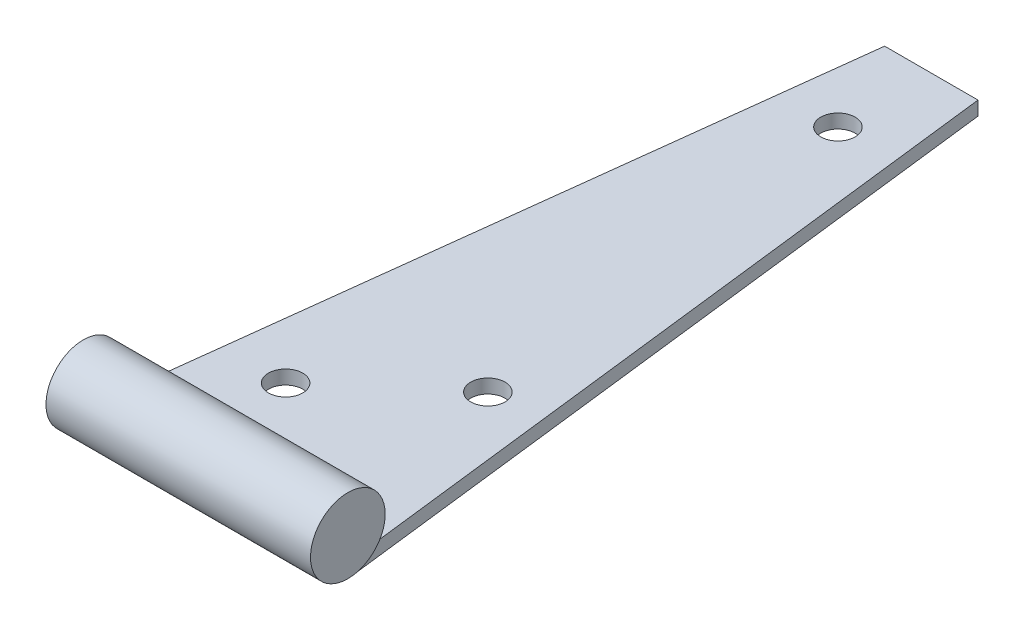
SolidWorks part; units mm, degrees
ref_plane "Front Plane" through (0, 0, 0) normal (0, 0, 1) x (1, 0, 0)
ref_plane "Top Plane" through (0, 0, 0) normal (0, 1, 0) x (1, 0, 0)
ref_plane "Right Plane" through (0, 0, 0) normal (1, 0, 0) x (0, 0, -1)
sketch "Sketch1" plane through (0, 0, 0) normal (0, 1, 0) x (1, 0, 0)
  line L0 (0, 0) -> (26.9875, 0)
  line L1 (13.4937, 0) -> (13.4937, 73.025) construction
  line L2 (18.2562, 73.025) -> (8.7312, 73.025)
  line L5 (0, 0) -> (8.7312, 73.025)
  line L6 (18.2562, 73.025) -> (26.9875, 0)
  point P8 (13.4937, 73.025)
extrude "Boss-Extrude1" add sketch "Sketch1" along normal blind 1.4224
sketch "Sketch2" plane through (0, 0, 0) normal (1, 0, 0) x (0, 0, -1)
  line L0 (0, 0) -> (0, 3.81) construction
  circle A0 centre (0, 3.81) radius 3.81
extrude "Boss-Extrude2" add sketch "Sketch2" along normal up to vertex up to point (26.9875, 1.4224, 0)
sketch "Sketch3" plane through (0, 1.4224, 0) normal (0, 1, 0) x (1, 0, 0)
  line L0 (13.4937, 73.025) -> (13.4937, -3.81) construction
  line L1 (18.2562, 73.025) -> (8.7312, 73.025) construction
  line L2 (0, -3.81) -> (26.9875, -3.81) construction
  line L3 (0, 0) -> (13.4937, 0) construction
  line L4 (13.4937, 0) -> (13.4938, 63.5) construction
  line L5 (13.4937, 0) -> (13.4938, 12.7) construction
  line L6 (13.4937, 0) -> (13.4938, 22.225) construction
  line L7 (13.4938, 12.7) -> (7.9375, 12.7) construction
  line L8 (13.4938, 22.225) -> (19.05, 22.225) construction
  circle A0 centre (13.4938, 63.5) radius 1.7526
  circle A1 centre (7.9375, 12.7) radius 1.7526
  circle A2 centre (19.05, 22.225) radius 1.7526
extrude "Cut-Extrude1" cut sketch "Sketch3" against normal blind 1.4224
